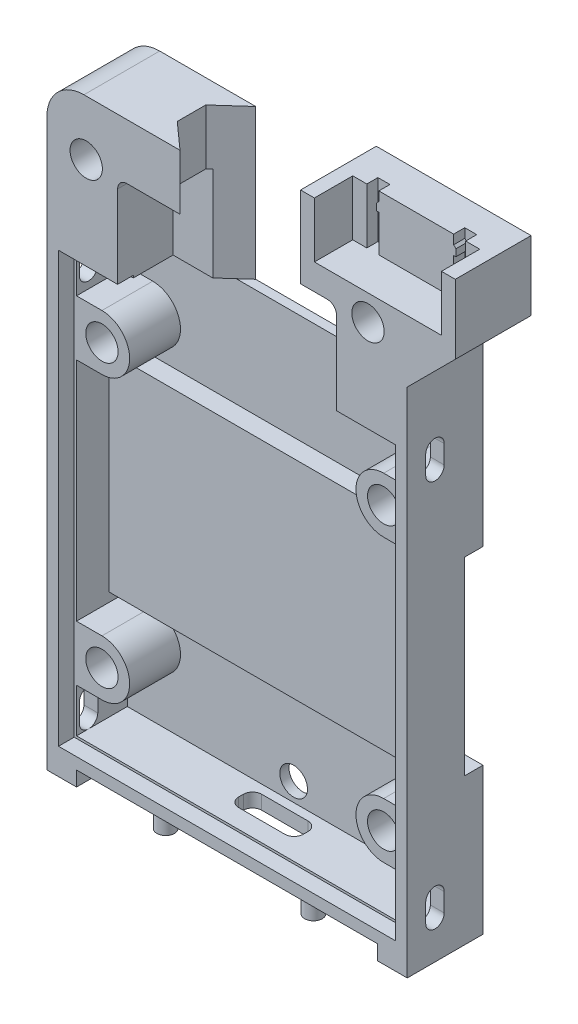
SolidWorks part; units mm, degrees
ref_plane "Front Plane" through (0, 0, 0) normal (0, 0, 1) x (1, 0, 0)
ref_plane "Top Plane" through (0, 0, 0) normal (0, 1, 0) x (1, 0, 0)
ref_plane "Right Plane" through (0, 0, 0) normal (1, 0, 0) x (0, 0, -1)
sketch "Sketch1" plane through (0, 0, 0) normal (0, 0, 1) x (1, 0, 0)
  line L0 (15.25, -20.35) -> (18, -20.35)
  line L1 (-19.5, -32.6) -> (19.5, -32.6)
  line L2 (-19.5, -32.6) -> (-19.5, 31.1)
  line L3 (-19.5, 31.1) -> (19.5, 31.1)
  line L4 (19.5, -32.6) -> (19.5, 31.1)
  line L5 (-15.25, -20.35) -> (-18, -20.35)
  line L6 (15.25, -26.35) -> (18, -26.35)
  line L7 (6.95, 31.1) -> (-15.5, 31.1) construction
  line L8 (-18, -31.1) -> (-18, 29.6)
  line L9 (-18, 29.6) -> (18, 29.6)
  line L10 (18, -31.1) -> (18, 29.6)
  line L11 (-18, -31.1) -> (18, -31.1)
  line L12 (-18, 14.9) -> (18, 14.9)
  line L13 (7.85, 14.9) -> (-4.95, 14.9) construction
  line L14 (-15.25, 4.15) -> (-18, 4.15)
  line L15 (-15.25, 10.15) -> (-18, 10.15)
  line L16 (15.25, 10.15) -> (18, 10.15)
  line L17 (15.25, 4.15) -> (18, 4.15)
  line L18 (-15.25, -26.35) -> (-18, -26.35)
  line L19 (19.5, -34.2) -> (19.5, -18.35) construction
  line L20 (-19.5, -34.2) -> (-19.5, -18.35) construction
  line L21 (15.3, -32.6) -> (-15.3, -32.6) construction
  line L22 (0, 31.1) -> (0, -32.6) construction
  line L23 (9.45, 26.9) -> (24.7, 26.9)
  line L24 (9.45, 26.9) -> (9.45, 33.9)
  line L25 (9.45, 33.9) -> (24.7, 33.9)
  line L26 (24.7, 26.9) -> (24.7, 33.9)
  line L27 (18, 29.6) -> (19.5, 31.1) construction
  line L28 (18.75, 30.35) -> (0, 30.35) construction
  line L29 (9.45, 26.9) -> (7.95, 26.9) construction
  line L30 (-7.95, 31.1) -> (7.95, 31.1)
  line L31 (-7.95, 31.1) -> (-7.95, 29.6)
  line L32 (-7.95, 29.6) -> (7.95, 29.6)
  line L33 (7.95, 31.1) -> (7.95, 29.6)
  line L34 (-7.95, 31.1) -> (7.95, 29.6) construction
  line L35 (-7.95, 29.6) -> (7.95, 31.1) construction
  line L36 (7.95, 26.9) -> (7.95, 29.6) construction
  line L37 (18, 29.6) -> (19.5, 29.6) construction
  line L38 (24.7, 26.4) -> (19.5, 21.2)
  line L39 (9.45, 33.9) -> (7.95, 33.9)
  line L40 (23.2, 33.9) -> (23.2, 26.9)
  line L41 (7.95, 33.9) -> (7.95, 31.1)
  line L42 (24.7, 30.4) -> (23.2, 30.4) construction
  line L43 (24.7, 26.9) -> (19.5, 26.9)
  line L44 (24.7, 26.9) -> (24.7, 26.4)
  line L45 (24.7, 26.4) -> (19.5, 26.4)
  line L46 (19.5, 26.9) -> (19.5, 26.4)
  circle A0 centre (15.25, -23.35) radius 1.75
  arc A1 (-15.5, 31.1) -> (-19.5, 27.1) centre (-15.5, 27.1) ccw construction
  circle A2 centre (15.25, -23.35) radius 3
  arc A3 (-15.5, 31.1) -> (-19.5, 27.1) centre (-15.5, 27.1) ccw
  arc A4 (-15.5, 29.6) -> (-18, 27.1) centre (-15.5, 27.1) ccw
  circle A6 centre (-15.25, -23.35) radius 1.75
  circle A7 centre (-15.25, -23.35) radius 1.75
  circle A8 centre (-15.25, 7.15) radius 1.75
  circle A9 centre (15.25, 7.15) radius 1.75
  circle A10 centre (15.25, 25.15) radius 1.75
  circle A11 centre (-15.25, 25.15) radius 1.75
  circle A12 centre (-15.25, -23.35) radius 3
  circle A13 centre (-15.25, -23.35) radius 3
  circle A14 centre (15.25, 7.15) radius 3
  circle A15 centre (-15.25, 7.15) radius 3
  dimension "D2" = 1.5
  dimension "D4" = 6
  dimension "D3" = 3.5
  dimension "D5" = 13.75
  dimension "D6" = 15.9
  dimension "D7" = 7
  dimension "D8" = 45
  dimension "D9" = 0.5
  dimension "D1" = 1.5
extrude "Base shape" add sketch "Sketch1" along normal up to surface (8.2 mm away) contours A15 L8 L9 L31 L3 A3 L2 L1 L4 L23 L10 A14 A2 L11 A12 | A12 L8 L18 | A12 L8 A6 | L8 A12 | A12 L5 L8 | A15 L8 L14 | A15 L8 A8 | L8 A15 | A15 L15 L8 | L23 A10 L24 L9 A4 L8 L12 L10 A11 | A4 L9 L8 | L33 L3 L31 L9 | L3 L33 L9 L24 | L24 L9 L10 L23 L4 L3 | L24 L23 L10 L9 | A14 L10 L16 | L10 A14 A9 | A14 L17 L10 | L10 A14 | L10 A2 L6 | A2 L10 A0 | L0 A2 L10 | A2 L10 | L40 L25 L24 L3 L4 L23 | L25 L40 L23 L26 | L38 L45 L4 | L45 L44 L23 L4 | L39 L41 L3 L24 region at (16.8481, -20.9099, 0) region at (17.3601, -20.8437, 0) region at (18.7469, -8.1, 0) region at (17.3601, -25.8563, 0) region at (18.1004, -23.35, 0) region at (17.3601, 4.6437, 0) region at (16.8481, 4.7099, 0) region at (18.1004, 7.15, 0) region at (17.3601, 9.6563, 0) region at (-17.3601, -25.8563, 0) region at (-0.6044, 21.831, 0) region at (-18.1004, -23.35, 0) region at (-17.9169, -23.35, 0) region at (13.725, 28.25, 0) region at (15.3803, 29.9053, 0) region at (-17.3601, -20.8437, 0) region at (22.1, 26.65, 0) region at (17.77, 31.4935, 0) region at (-17.3601, 9.6563, 0) region at (-17.4416, 29.0416, 0) region at (8.7, 30.35, 0) region at (21.2333, 24.6667, 0) region at (23.95, 30.4, 0) region at (-16.8481, 9.5901, 0) region at (-18.1004, 7.15, 0) region at (-17.3601, 4.6437, 0) region at (0, 30.35, 0) region at (8.7, 32.5, 0)
sketch "Sketch3" plane through (19.5, 0, 0) normal (1, 0, 0) x (0, 0, -1)
  line L1 (0, -18.35) -> (-2, -18.35)
  line L2 (0, -18.35) -> (0, 2.15)
  line L3 (0, 2.15) -> (-2, 2.15)
  line L4 (-2, -18.35) -> (-2, 2.15)
  line L5 (0, -18.35) -> (1.75, -18.35) construction
  line L6 (0, 2.15) -> (1.75, 2.15) construction
  line L7 (0, -32.6) -> (0, 21.2) construction
  dimension "D1" = 2
extrude "Strap cut" cut sketch "Sketch3" against normal through all
sketch "Sketch4" plane through (0, 31.1, 0) normal (0, 1, 0) x (1, 0, 0)
  line L2 (7.95, 0) -> (-5.0998, 0)
  line L4 (-15.5, 0) -> (7.95, 0) construction
  line L5 (-15.5, -8.2) -> (7.95, -8.2) construction
  line L6 (7.95, -8.2) -> (-5.0998, -8.2)
  line L12 (7.95, -8.3) -> (7.95, 0.1)
  line L13 (7.95, 0.1) -> (-4.9883, 0.1)
  line L14 (-4.9883, 0.1) -> (-7.95, -2.5553)
  line L15 (-7.95, -2.5553) -> (-7.95, -5.6447)
  line L16 (-7.95, -5.6447) -> (-4.9883, -8.3)
  line L17 (-4.9883, -8.3) -> (7.95, -8.3)
  line L18 (7.95, -8.3) -> (7.95, 0.1)
  line L19 (7.95, 0.1) -> (-4.9883, 0.1)
  line L20 (-4.9883, 0.1) -> (-7.95, -2.5553)
  line L21 (-7.95, -2.5553) -> (-7.95, -5.6447)
  line L22 (-7.95, -5.6447) -> (-4.9883, -8.3)
  line L23 (-4.9883, -8.3) -> (7.95, -8.3)
  dimension "D1" = 0.1
extrude "XT60 cut" cut sketch "Sketch4" against normal up to next contours L21 L22 L18 L20 region at (0.4142, 31.1, 4.1)
sketch "Sketch5" plane through (19.5, 0, 0) normal (1, 0, 0) x (0, 0, -1)
  line L1 (-8.2, -32.6) -> (-8.2, 21.2) construction
  line L2 (-6.2, -31.1) -> (-4.2, -31.1)
  line L3 (-6.2, -31.1) -> (-6.2, -27.1)
  line L4 (-6.2, -27.1) -> (-4.2, -27.1)
  line L5 (-4.2, -31.1) -> (-4.2, -27.1)
  line L6 (-8.2, -31.1) -> (0, -31.1) construction
  line L7 (-8.2, 14.9) -> (0, 14.9) construction
  line L8 (-6.2, 14.9) -> (-4.2, 14.9)
  line L9 (-6.2, 14.9) -> (-6.2, 10.9)
  line L10 (-6.2, 10.9) -> (-4.2, 10.9)
  line L11 (-4.2, 14.9) -> (-4.2, 10.9)
  line L14 (-5.2, -27.1) -> (-5.2, -31.1) construction
  line L15 (-5.2, 14.9) -> (-5.2, 10.9) construction
  circle A0 centre (-5.2, -28.1) radius 1
  circle A1 centre (-5.2, -30.1) radius 1
  circle A2 centre (-5.2, 13.9) radius 1
  circle A3 centre (-5.2, 11.9) radius 1
  point P20 (-5.2, -29.1)
  point P31 (-5.2, 12.9)
  dimension "D3" = 4
  dimension "D1" = 2
  dimension "D2" = 2
extrude "Power wires cut" cut sketch "Sketch5" against normal through all contours A2 | A3 | A3 A2 L9 | A3 L11 A2 | A1 | A0 | A1 L5 A0 | A1 A0 L3 region at (19.5, -30.1, 5.2) region at (19.5, -29.1, 5.9766) region at (19.5, -29.1, 4.4234) region at (19.5, -28.1, 5.2) region at (19.5, 13.9, 5.2) region at (19.5, 12.9, 5.9766) region at (19.5, 12.9, 4.4234) region at (19.5, 11.9, 5.2)
sketch "Sketch6" plane through (0, 0, 8.2) normal (0, 0, 1) x (1, 0, 0)
  line L0 (8.85, 14.9) -> (10.85, 14.9) construction
  line L1 (11.85, 24.1) -> (11.85, 15.9) construction
  line L3 (-11.85, 14.9) -> (11.85, 14.9)
  line L4 (-11.85, 24.1) -> (-11.85, 15.9) construction
  line L5 (11.85, 24.1) -> (11.85, 15.9)
  line L6 (10.85, 25.1) -> (-10.85, 25.1)
  line L7 (-11.85, 24.1) -> (-11.85, 15.9)
  line L8 (-11.85, 15.9) -> (-11.85, 14.9)
  line L9 (11.85, 15.9) -> (11.85, 14.9)
  arc A2 (-10.85, 25.1) -> (-11.85, 24.1) centre (-10.85, 24.1) ccw construction
  arc A3 (-10.85, 25.1) -> (-11.85, 24.1) centre (-10.85, 24.1) ccw
  arc A4 (11.85, 24.1) -> (10.85, 25.1) centre (10.85, 24.1) ccw construction
  arc A5 (11.85, 24.1) -> (10.85, 25.1) centre (10.85, 24.1) ccw
  line M1 (7.95, 33.9) -> (7.95, 14.9)
  line M15 (-5.0998, 14.9) -> (-5.0998, 31.1)
  line M118 (7.95, 14.9) -> (18, 14.9)
  line M134 (-18, 14.9) -> (-5.0998, 14.9)
extrude "IO wires cut" cut sketch "Sketch6" against normal blind 6 contours L7 L8 M134 M15 | L3 M15 M1 | L5 L9 M1 M118 region at (-8.465, 19.9848, 8.2) region at (1.4251, 20, 8.2) region at (9.8906, 19.9735, 8.2)
sketch "Sketch7" plane through (-18, 0, 0) normal (1, 0, 0) x (0, 0, -1)
  line L6 (0, -18.35) -> (0, -20.35)
  line L7 (-2, -18.35) -> (0, -18.35)
  line L8 (-2, 2.15) -> (-2, -18.35)
  line L9 (0, 2.15) -> (-2, 2.15)
  line L12 (0, 3.15) -> (-3, 3.15)
  line L13 (-3, 3.15) -> (-3, -19.35)
  line L14 (-3, -19.35) -> (-1, -19.35)
  line L15 (-1, -19.35) -> (-1, -20.35)
  line L16 (-1, -20.35) -> (0, -20.35)
  line L17 (0, 3.15) -> (-1, 3.15)
  line L19 (0, -31.1) -> (-1, -31.1)
  line L22 (0, -31.1) -> (0, -20.35)
  line L23 (0, -20.35) -> (-1, -20.35)
  line L24 (-1, -31.1) -> (-1, -20.35)
  line L25 (0, 3.15) -> (0, 14.9)
  line L26 (0, 14.9) -> (-1, 14.9)
  line L27 (-1, 3.15) -> (-1, 14.9)
  line L28 (-5.2, 14.9) -> (0, 14.9) construction
  line L31 (0, -20.35) -> (0, -18.35) construction
  line L32 (0, 2.15) -> (-2, 2.15) construction
  line M48 (0, -20.35) -> (0, -18.35)
  line M49 (0, -18.35) -> (-2, -18.35)
  line M50 (-2, -18.35) -> (-2, 2.15)
  line M51 (-2, 2.15) -> (0, 2.15)
  line M52 (0, 2.15) -> (0, 4.15)
  line M53 (0, 4.15) -> (-8.2, 4.15)
  line M55 (-8.2, -20.35) -> (0, -20.35)
  dimension "D1" = 1
extrude "Bottom" add sketch "Sketch7" along normal up to surface (36 mm away) contours L27 L25 L26 M53 | L27 L12 M52 M53 | L14 L15 L12 L13 M55 M48 M49 M50 M51 M52 | L24 L19 L22 M55 region at (-18, -8.5273, 2.2091) region at (-18, -25.725, 0.5) region at (-18, 3.65, 0.5) region at (-18, 9.525, 0.5) up to face at (18, -8.1, 2.55)
sketch "Sketch9" plane through (0, 0, 0) normal (0, 0, -1) x (-1, 0, 0)
  circle A0 centre (15.25, -23.35) radius 1.75 construction
  circle A1 centre (-15.25, 7.15) radius 1.75 construction
  circle A2 centre (15.25, 7.15) radius 1.75 construction
  circle A3 centre (15.25, -23.35) radius 1.75 construction
  circle A4 centre (15.25, -23.35) radius 1.75
  circle A5 centre (-15.25, 7.15) radius 1.75
  circle A6 centre (15.25, 7.15) radius 1.75
  circle A7 centre (15.25, -23.35) radius 1.75
  circle A8 centre (-15.25, -23.35) radius 1.75 construction
  circle A9 centre (-15.25, -23.35) radius 1.75
extrude "Bottom holes" cut sketch "Sketch9" against normal up to next contours A5 | A6 | A4 | A9 region at (-15.25, -23.35, 0) region at (15.25, 7.15, 0) region at (-15.25, 7.15, 0) region at (15.25, -23.35, 0)
sketch "Sketch8" plane through (0, 0, 8.2) normal (0, 0, 1) x (1, 0, 0)
  line L0 (-6.2152, 14.9) -> (-18, 14.9) construction
  line L1 (-18.25, 15.15) -> (18.25, 15.15)
  line L2 (-18.25, 15.15) -> (-18.25, -31.35)
  line L3 (-18.25, -31.35) -> (18.25, -31.35)
  line L4 (18.25, 15.15) -> (18.25, -31.35)
  line L5 (-18, 14.9) -> (-18.25, 14.9) construction
  line L6 (-18, 14.9) -> (-18, 15.15) construction
  line L7 (18, 14.9) -> (18.25, 14.9) construction
  line L8 (-18, -31.1) -> (-18, -31.35) construction
  dimension "D1" = 0.25
extrude "PCB cut" cut sketch "Sketch8" against normal blind 1.7
sketch "Sketch11" plane through (0, -32.6, 0) normal (0, -1, 0) x (1, 0, 0)
  line L0 (19.5, 8.2) -> (19.5, 0) construction
  line L1 (-19.5, 8.2) -> (19.5, 8.2)
  line L2 (-19.5, 8.2) -> (-19.5, -1.8)
  line L3 (-19.5, -1.8) -> (19.5, -1.8)
  line L4 (19.5, 8.2) -> (19.5, -1.8)
  line L5 (-19.5, 3.2) -> (19.5, 3.2) construction
  line L6 (0, -1.8) -> (0, 8.2) construction
  line L8 (-2.5, 4.45) -> (2.5, 4.45)
  line L9 (-3.5, 3.45) -> (-3.5, 2.95)
  line L10 (-2.5, 1.95) -> (2.5, 1.95)
  line L11 (3.5, 3.45) -> (3.5, 2.95)
  line L12 (-3.5, 4.45) -> (3.5, 1.95) construction
  line L13 (-3.5, 1.95) -> (3.5, 4.45) construction
  arc A0 (2.5, 4.45) -> (3.5, 3.45) centre (2.5, 3.45) cw
  arc A1 (2.5, 1.95) -> (3.5, 2.95) centre (2.5, 2.95) ccw
  arc A2 (-3.5, 2.95) -> (-2.5, 1.95) centre (-2.5, 2.95) ccw
  arc A3 (-2.5, 4.45) -> (-3.5, 3.45) centre (-2.5, 3.45) ccw
  point P11 (0, 3.2)
  dimension "D4" = 1
  dimension "D1" = 10
  dimension "D2" = 7
  dimension "D3" = 2.5
extrude "Ledbar wires cut" cut sketch "Sketch11" against normal up to next contours L8 A3 L9 A2 L10 A1 L11 A0 region at (0, -32.6, 3.2)
sketch "Sketch13" plane through (0, -32.6, 0) normal (0, -1, 0) x (1, 0, 0)
  line L0 (-19.5, 8.2) -> (19.5, 8.2) construction
  line L1 (19.5, 0) -> (16.3, 0)
  line L2 (19.5, 0) -> (19.5, 8.2)
  line L3 (19.5, 8.2) -> (16.3, 8.2)
  line L4 (16.3, 0) -> (16.3, 8.2)
  line L5 (16.1, -1.8) -> (16.1, 8.2) construction
  line L6 (0, 8.2) -> (0, 0) construction
  line L7 (-19.5, 0) -> (-16.3, 0)
  line L8 (-19.5, 0) -> (-19.5, 8.2)
  line L9 (-19.5, 8.2) -> (-16.3, 8.2)
  line L10 (-16.3, 0) -> (-16.3, 8.2)
  dimension "D1" = 0.2
extrude "Ledbar sides" add sketch "Sketch13" along normal blind 1.6
sketch "Sketch14" plane through (0, -32.6, 0) normal (0, -1, 0) x (1, 0, 0)
  circle A0 centre (8, 6.85) radius 0.95
  circle A1 centre (-8, 6.85) radius 0.95
  dimension "D1" = 1.9
extrude "Ledbar mounts" add sketch "Sketch14" along normal blind 2
sketch "Sketch16" plane through (0, 33.9, 0) normal (0, 1, 0) x (1, 0, 0)
  line L0 (7.95, -6.125) -> (24.7, -6.125) construction
  line L1 (7.95, -8.2) -> (24.7, -8.2) construction
  line L2 (21.675, -2.85) -> (20.375, -2.85)
  line L3 (20.375, -4.05) -> (20.375, -2.85)
  line L4 (9.45, -4.05) -> (23.2, -4.05)
  line L5 (9.45, -4.05) -> (9.45, -8.2)
  line L6 (9.45, -8.2) -> (23.2, -8.2)
  line L7 (23.2, -4.05) -> (23.2, -8.2)
  line L8 (9.45, -4.05) -> (23.2, -8.2) construction
  line L9 (9.45, -8.2) -> (23.2, -4.05) construction
  line L10 (24.7, -8.2) -> (24.7, 0) construction
  line L11 (7.95, -8.2) -> (7.95, 0) construction
  line L12 (16.325, -8.2) -> (16.325, -4.05) construction
  line L13 (11.625, -2.85) -> (11.625, -4.05) construction
  line L14 (10.975, -4.05) -> (12.275, -4.05)
  line L15 (10.975, -4.05) -> (10.975, -2.85)
  line L16 (10.975, -2.85) -> (12.275, -2.85)
  line L17 (12.275, -4.05) -> (12.275, -2.85)
  line L18 (10.975, -2.85) -> (10.975, -8.2) construction
  line L19 (21.675, -4.05) -> (21.675, -2.85)
  point P6 (16.325, -6.125)
  dimension "D1" = 13.75
  dimension "D2" = 4.15
  dimension "D3" = 1.3
  dimension "D4" = 1.2
  dimension "D5" = 4.7
extrude "Balance plug cut" cut sketch "Sketch16" against normal blind 6 contours L7 L4 L5 L6 | L4 L17 L16 L15 | L4 L19 L2 L3 region at (21.025, 33.9, 3.45) region at (16.325, 33.9, 6.125) region at (11.625, 33.9, 3.45)
sketch "Sketch17" plane through (0, 0, 2.85) normal (0, 0, 1) x (1, 0, 0)
  line L0 (16.325, 33.9) -> (16.325, 27.9) construction
  line L1 (12.275, 33.9) -> (20.375, 33.9) construction
  line L2 (12.275, 27.9) -> (20.375, 27.9) construction
  line L3 (12.275, 27.9) -> (12.275, 33.9) construction
  line L4 (12.025, 32.9) -> (20.625, 32.9)
  line L5 (12.025, 32.9) -> (12.025, 31.9)
  line L6 (12.025, 31.9) -> (20.625, 31.9)
  line L7 (20.625, 32.9) -> (20.625, 31.9)
  line L8 (12.025, 32.9) -> (20.625, 31.9) construction
  line L9 (12.025, 31.9) -> (20.625, 32.9) construction
  line L10 (12.025, 32.65) -> (12.275, 32.9)
  line L11 (20.625, 32.65) -> (20.375, 32.9)
  point P6 (16.325, 32.4)
  line M7 (20.375, 33.9) -> (20.375, 27.9)
  dimension "D1" = 0.25
  dimension "D2" = 1
  dimension "D3" = 1
  dimension "D4" = 45
extrude "Balance plug locks" add sketch "Sketch17" along normal up to surface (1.2 mm away) contours L10 L5 L6 L4 M7 | L7 L11 L6 M7 region at (16.2154, 32.3984, 2.85) region at (20.494, 32.3405, 2.85) up to face at (10.2125, 30.9, 4.05)
sketch "Sketch18" plane through (0, 0, 0) normal (0, 0, -1) x (-1, 0, 0)
  line L0 (0, -32.6) -> (0, -18.35) construction
  line L1 (16.3, -32.6) -> (-16.3, -32.6) construction
  line L2 (19.5, -18.35) -> (-19.5, -18.35) construction
  line L3 (-19.5, -30.6) -> (19.5, -30.6) construction
  line L4 (-19.5, -34.2) -> (-19.5, -18.35) construction
  line L5 (19.5, -34.2) -> (19.5, -18.35) construction
  circle A0 centre (0, -29.1) radius 1.5
  dimension "D2" = 3
  dimension "D1" = 2
extrude "PDB removal hole" cut sketch "Sketch18" against normal up to next
sketch "Sketch10" [suppressed] plane through (0, 0, 2) normal (0, 0, -1) x (-1, 0, 0)
  line L0 (0, 2.15) -> (0, -18.35) construction
  line L1 (19.5, 2.15) -> (-19.5, 2.15) construction
  line L2 (19.5, -18.35) -> (-19.5, -18.35) construction
  line L3 (19.5, 2.15) -> (19.5, -18.35) construction
  line L4 (-19.5, 1.15) -> (19.5, 1.15)
  line L5 (-19.5, 1.15) -> (-19.5, 0.65)
  line L6 (-19.5, 0.65) -> (19.5, 0.65)
  line L7 (19.5, 1.15) -> (19.5, 0.65)
  line L8 (-19.5, 1.15) -> (19.5, 0.65) construction
  line L9 (-19.5, 0.65) -> (19.5, 1.15) construction
  line L10 (-19.5, 2.15) -> (19.5, 2.15) construction
  line L11 (-19.5, -1.35) -> (19.5, -1.35)
  line L12 (19.5, -0.85) -> (19.5, -1.35)
  line L13 (-19.5, -0.85) -> (19.5, -0.85)
  line L14 (-19.5, -0.85) -> (-19.5, -1.35)
  line L15 (-19.5, -3.35) -> (19.5, -3.35)
  line L16 (19.5, -2.85) -> (19.5, -3.35)
  line L17 (-19.5, -2.85) -> (19.5, -2.85)
  line L18 (-19.5, -2.85) -> (-19.5, -3.35)
  line L19 (-19.5, -5.35) -> (19.5, -5.35)
  line L20 (19.5, -4.85) -> (19.5, -5.35)
  line L21 (-19.5, -4.85) -> (19.5, -4.85)
  line L22 (-19.5, -4.85) -> (-19.5, -5.35)
  line L23 (-19.5, -7.35) -> (19.5, -7.35)
  line L24 (19.5, -6.85) -> (19.5, -7.35)
  line L25 (-19.5, -6.85) -> (19.5, -6.85)
  line L26 (-19.5, -6.85) -> (-19.5, -7.35)
  line L27 (-19.5, -9.35) -> (19.5, -9.35)
  line L28 (19.5, -8.85) -> (19.5, -9.35)
  line L29 (-19.5, -8.85) -> (19.5, -8.85)
  line L30 (-19.5, -8.85) -> (-19.5, -9.35)
  line L31 (-19.5, -11.35) -> (19.5, -11.35)
  line L32 (19.5, -10.85) -> (19.5, -11.35)
  line L33 (-19.5, -10.85) -> (19.5, -10.85)
  line L34 (-19.5, -10.85) -> (-19.5, -11.35)
  line L35 (-19.5, -13.35) -> (19.5, -13.35)
  line L36 (19.5, -12.85) -> (19.5, -13.35)
  line L37 (-19.5, -12.85) -> (19.5, -12.85)
  line L38 (-19.5, -12.85) -> (-19.5, -13.35)
  line L39 (-19.5, -15.35) -> (19.5, -15.35)
  line L40 (19.5, -14.85) -> (19.5, -15.35)
  line L41 (-19.5, -14.85) -> (19.5, -14.85)
  line L42 (-19.5, -14.85) -> (-19.5, -15.35)
  line L43 (-19.5, -17.35) -> (19.5, -17.35)
  line L44 (19.5, -16.85) -> (19.5, -17.35)
  line L45 (-19.5, -16.85) -> (19.5, -16.85)
  line L46 (-19.5, -16.85) -> (-19.5, -17.35)
  point P6 (0, 0.9)
  dimension "D1" = 1
  dimension "D2" = 0.5
  dimension "D4" = 2
  dimension "D3" = 10
extrude "3D print ribs" [suppressed] add sketch "Sketch10" along normal up to surface (2 mm away) up to face at (-1.5, -29.1, 0)
sketch "Sketch15" [suppressed] plane through (0, 0, 0) normal (0, 0, -1) x (-1, 0, 0)
  line L0 (-8, -34.6) -> (-8, -32.6) construction
  line L1 (-8.95, -34.6) -> (-7.05, -34.6) construction
  line L2 (-8.95, -32.6) -> (-7.05, -32.6) construction
  line L3 (0, -32.6) -> (0, 14.9) construction
  line L4 (-8.25, -34.6) -> (-7.75, -34.6)
  line L5 (-8.25, -34.6) -> (-8.25, -32.6)
  line L6 (-8.25, -32.6) -> (-7.75, -32.6)
  line L7 (-7.75, -34.6) -> (-7.75, -32.6)
  line L8 (-8.25, -34.6) -> (-7.75, -32.6) construction
  line L9 (-8.25, -32.6) -> (-7.75, -34.6) construction
  line L10 (16.3, -32.6) -> (-16.3, -32.6) construction
  line L11 (-7.95, 14.9) -> (5.0998, 14.9) construction
  line L12 (8.25, -32.6) -> (7.75, -32.6)
  line L13 (7.75, -34.6) -> (7.75, -32.6)
  line L14 (8.25, -34.6) -> (7.75, -34.6)
  line L15 (8.25, -34.6) -> (8.25, -32.6)
  point P6 (-8, -33.6)
  dimension "D1" = 0.5
extrude "3D print led supports" [suppressed] add sketch "Sketch15" against normal up to next
